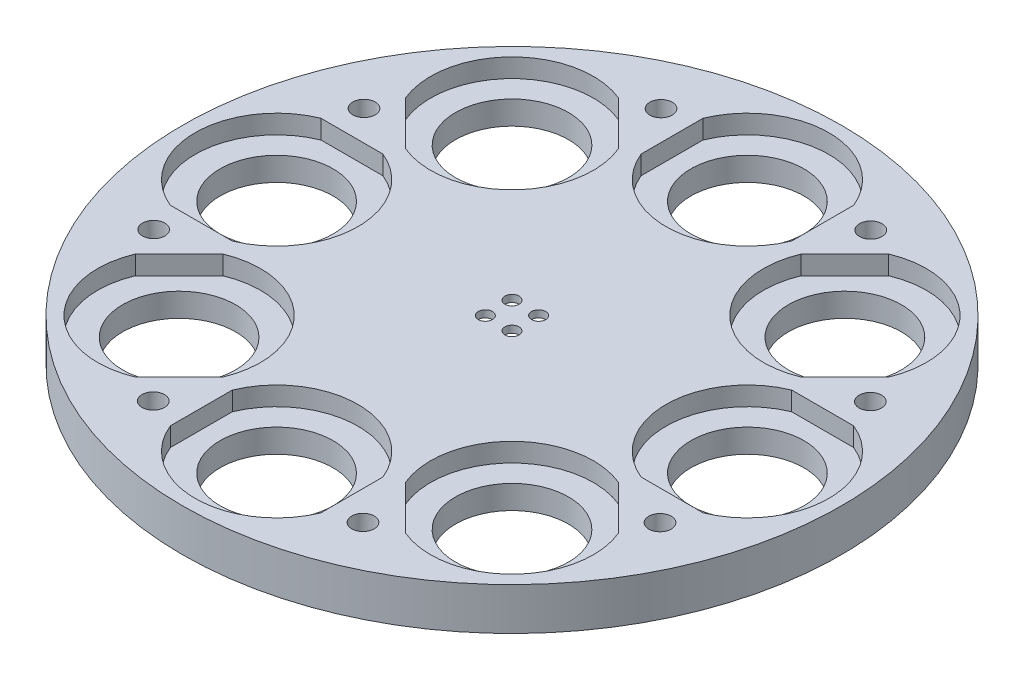
SolidWorks part; units mm, degrees
ref_plane "Front Plane" through (0, 0, 0) normal (0, 0, 1) x (1, 0, 0)
ref_plane "Top Plane" through (0, 0, 0) normal (0, 1, 0) x (1, 0, 0)
ref_plane "Right Plane" through (0, 0, 0) normal (1, 0, 0) x (0, 0, -1)
sketch "Sketch1" plane through (0, 0, 0) normal (0, 1, 0) x (1, 0, 0)
  line L0 (70, 0) -> (50, 0) construction
  circle A0 centre (0, 0) radius 70
  circle A1 centre (50, 0) radius 12
  circle A2 centre (35.3553, -35.3553) radius 12
  circle A3 centre (0, -50) radius 12
  circle A4 centre (-35.3553, -35.3553) radius 12
  circle A5 centre (-50, 0) radius 12
  circle A6 centre (-35.3553, 35.3553) radius 12
  circle A7 centre (0, 50) radius 12
  circle A8 centre (35.3553, 35.3553) radius 12
  point P23 (0, 0)
  dimension "D1" = 140
  dimension "D3" = 24
  dimension "D2" = 20
  dimension "D4" = 8
extrude "Boss-Extrude1" add sketch "Sketch1" along normal blind 25
sketch "Sketch2" plane through (0, 25, 0) normal (0, 1, 0) x (1, 0, 0)
  line L0 (50, 0) -> (50, 16) construction
  line L1 (50, 16) -> (43.4205, 16)
  line L2 (50, 16) -> (56.5795, 16)
  line L3 (32.7, 0) -> (67.3, 0) construction
  line L4 (50, -16) -> (56.5795, -16)
  line L5 (50, -16) -> (43.4205, -16)
  line L6 (46.669, -24.0416) -> (42.0166, -19.3892)
  line L7 (24.0416, -46.669) -> (19.3892, -42.0166)
  line L8 (24.0416, -46.669) -> (28.694, -51.3215)
  line L9 (46.669, -24.0416) -> (51.3215, -28.694)
  line L10 (16, -50) -> (16, -43.4205)
  line L11 (-16, -50) -> (-16, -43.4205)
  line L12 (-16, -50) -> (-16, -56.5795)
  line L13 (16, -50) -> (16, -56.5795)
  line L14 (-24.0416, -46.669) -> (-19.3892, -42.0166)
  line L15 (-46.669, -24.0416) -> (-42.0166, -19.3892)
  line L16 (-46.669, -24.0416) -> (-51.3215, -28.694)
  line L17 (-24.0416, -46.669) -> (-28.694, -51.3215)
  line L18 (-50, -16) -> (-43.4205, -16)
  line L19 (-50, 16) -> (-43.4205, 16)
  line L20 (-50, 16) -> (-56.5795, 16)
  line L21 (-50, -16) -> (-56.5795, -16)
  line L22 (-46.669, 24.0416) -> (-42.0166, 19.3892)
  line L23 (-24.0416, 46.669) -> (-19.3892, 42.0166)
  line L24 (-24.0416, 46.669) -> (-28.694, 51.3215)
  line L25 (-46.669, 24.0416) -> (-51.3215, 28.694)
  line L26 (-16, 50) -> (-16, 43.4205)
  line L27 (16, 50) -> (16, 43.4205)
  line L28 (16, 50) -> (16, 56.5795)
  line L29 (-16, 50) -> (-16, 56.5795)
  line L30 (24.0416, 46.669) -> (19.3892, 42.0166)
  line L31 (46.669, 24.0416) -> (42.0166, 19.3892)
  line L32 (46.669, 24.0416) -> (51.3215, 28.694)
  line L33 (24.0416, 46.669) -> (28.694, 51.3215)
  arc A0 (43.4205, 16) -> (43.4205, -16) centre (50, 0) ccw
  arc A1 (56.5795, -16) -> (56.5795, 16) centre (50, 0) ccw
  arc A2 (42.0166, -19.3892) -> (19.3892, -42.0166) centre (35.3553, -35.3553) ccw
  arc A3 (28.694, -51.3215) -> (51.3215, -28.694) centre (35.3553, -35.3553) ccw
  arc A4 (16, -43.4205) -> (-16, -43.4205) centre (0, -50) ccw
  arc A5 (-16, -56.5795) -> (16, -56.5795) centre (0, -50) ccw
  arc A6 (-19.3892, -42.0166) -> (-42.0166, -19.3892) centre (-35.3553, -35.3553) ccw
  arc A7 (-51.3215, -28.694) -> (-28.694, -51.3215) centre (-35.3553, -35.3553) ccw
  arc A8 (-43.4205, -16) -> (-43.4205, 16) centre (-50, 0) ccw
  arc A9 (-56.5795, 16) -> (-56.5795, -16) centre (-50, 0) ccw
  arc A10 (-42.0166, 19.3892) -> (-19.3892, 42.0166) centre (-35.3553, 35.3553) ccw
  arc A11 (-28.694, 51.3215) -> (-51.3215, 28.694) centre (-35.3553, 35.3553) ccw
  arc A12 (-16, 43.4205) -> (16, 43.4205) centre (0, 50) ccw
  arc A13 (16, 56.5795) -> (-16, 56.5795) centre (0, 50) ccw
  arc A14 (19.3892, 42.0166) -> (42.0166, 19.3892) centre (35.3553, 35.3553) ccw
  arc A15 (51.3215, 28.694) -> (28.694, 51.3215) centre (35.3553, 35.3553) ccw
  point P61 (0, 0)
  dimension "D1" = 34.6
  dimension "D2" = 16
  dimension "D3" = 8
extrude "Cut-Extrude1" cut sketch "Sketch2" against normal blind 10
ref_plane "Plane1" through (0, 10, 0) normal (0, 1, 0) x (1, 0, 0)
split "Split1" trim tools "Plane1" bodies to split 102 resulting bodies 103 104
delete or keep bodies "Body-Delete/Keep 1" type delete bodies bodies 104
sketch "Sketch3" plane through (0, 10, 0) normal (0, -1, 0) x (1, 0, 0)
  circle A0 centre (0, 0) radius 20
  dimension "D1" = 40
extrude "Cut-Extrude2" cut sketch "Sketch3" against normal blind 7.5
sketch "Sketch4" plane through (0, 25, 0) normal (0, 1, 0) x (1, 0, 0)
  circle A0 centre (0, 0) radius 70
extrude "Cut-Extrude3" cut sketch "Sketch4" against normal blind 6
sketch "Sketch5" plane through (0, 17.5, 0) normal (0, -1, 0) x (1, 0, 0)
  circle A0 centre (2.8254, 2.8314) radius 1.5
  circle A1 centre (2.8314, -2.8254) radius 1.5
  circle A2 centre (-2.8254, -2.8314) radius 1.5
  circle A3 centre (-2.8314, 2.8254) radius 1.5
  dimension "D1" = 3
extrude "Cut-Extrude4" cut sketch "Sketch5" against normal through all
sketch "Sketch7" plane through (0, 19, 0) normal (0, 1, 0) x (1, 0, 0)
  circle A0 centre (-22.2295, 53.882) radius 2.3813
  circle A1 centre (22.3817, 53.819) radius 2.3813
  circle A2 centre (53.882, 22.2295) radius 2.3813
  circle A3 centre (53.819, -22.3817) radius 2.3813
  circle A4 centre (22.2295, -53.882) radius 2.3813
  circle A5 centre (-22.3817, -53.819) radius 2.3813
  circle A6 centre (-53.882, -22.2295) radius 2.3812
  circle A7 centre (-53.819, 22.3817) radius 2.3812
  point P20 (0, 0)
  dimension "D1" = 4.7625
  dimension "D2" = 8
extrude "Cut-Extrude5" cut sketch "Sketch7" against normal through all
sketch "Sketch8" plane through (0, 19, 0) normal (0, 1, 0) x (1, 0, 0)
  line L2 (-16, 56.5795) -> (-16, 43.4205)
  line L3 (16, 43.4205) -> (16, 56.5795)
  line L4 (-16, 56.5795) -> (-16, 43.4205)
  line L5 (16, 43.4205) -> (16, 56.5795)
  circle A0 centre (0, 50) radius 12 construction
  circle A1 centre (0, 50) radius 12
  arc A2 (16, 56.5795) -> (-16, 56.5795) centre (0, 50) ccw
  arc A3 (-16, 43.4205) -> (16, 43.4205) centre (0, 50) ccw
  arc A4 (16, 56.5795) -> (-16, 56.5795) centre (0, 50) ccw
  arc A5 (-16, 43.4205) -> (16, 43.4205) centre (0, 50) ccw
  dimension "D1" = 0
